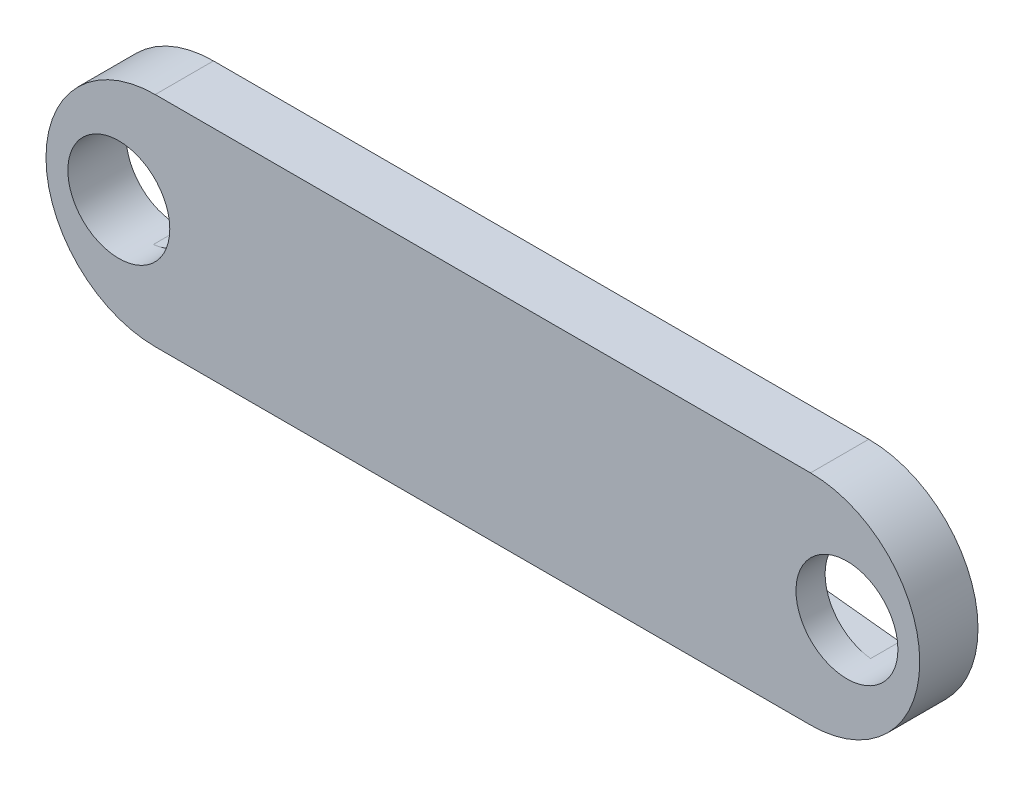
SolidWorks part; units mm, degrees
ref_plane "Front Plane" through (0, 0, 0) normal (0, 0, 1) x (1, 0, 0)
ref_plane "Top Plane" through (0, 0, 0) normal (0, 1, 0) x (1, 0, 0)
ref_plane "Right Plane" through (0, 0, 0) normal (1, 0, 0) x (0, 0, -1)
sketch "Sketch1" plane through (0, 0, 0) normal (0, 0, 1) x (1, 0, 0)
  line L1 (-55, 16.6867) -> (5, 16.6867)
  line L2 (-55, 16.6867) -> (-55, 1.6867)
  line L3 (-55, 1.6867) -> (5, 1.6867)
  line L4 (5, 16.6867) -> (5, 1.6867)
  line L5 (-55, 16.6867) -> (5, 1.6867) construction
  line L6 (-55, 1.6867) -> (5, 16.6867) construction
  circle A0 centre (-50, 9.1867) radius 1
  circle A1 centre (0, 9.1867) radius 1
  point P0 (-25, 9.1867)
  dimension "D1" = 60
  dimension "D2" = 15
extrude "Boss-Extrude1" add sketch "Sketch1" along normal blind 4
fillet "Fillet1" 2 edges at (5, 16.6867, 2) (5, 1.6867, 2) type full round first side face at (-25, 16.6867, 2) second side face at (-25, 1.6867, 2) middle face at (5, 9.1867, 2)
fillet "Fillet2" 2 edges at (-55, 1.6867, 2) (-55, 16.6867, 2) type full round first side face at (-28.75, 1.6867, 2) second side face at (-28.75, 16.6867, 2) middle face at (-55, 9.1867, 2)
sketch "Sketch3" plane through (0, 0, 0) normal (0, 0, -1) x (-1, 0, 0)
  line L0 (14.2143, 11.1752) -> (0.375, 12.6666)
  line L1 (14.2143, 7.1983) -> (0.375, 5.7069)
  arc A0 (0.375, 5.7069) -> (0.375, 12.6666) centre (0, 9.1867) cw
  arc A1 (14.2143, 11.1752) -> (14.2143, 7.1983) centre (14, 9.1867) cw
extrude "Cut-Extrude1" cut sketch "Sketch3" against normal blind 2
sketch "Sketch4" plane through (0, 0, 2) normal (0, 0, -1) x (-1, 0, 0)
  circle A1 centre (0, 9.1867) radius 3.5
extrude "Cut-Extrude2" cut sketch "Sketch4" against normal blind 6
sketch "Sketch5" plane through (0, 0, 0) normal (0, 0, -1) x (-1, 0, 0)
  line L0 (49.625, 12.6666) -> (35.7857, 11.1752)
  line L1 (35.7857, 7.1983) -> (49.625, 5.7069)
  arc A0 (49.625, 12.6666) -> (49.625, 5.7069) centre (50, 9.1867) cw
  arc A1 (35.7857, 11.1752) -> (35.7857, 7.1983) centre (36, 9.1867) ccw
extrude "Cut-Extrude3" cut sketch "Sketch5" against normal blind 2
sketch "Sketch6" plane through (0, 0, 0) normal (0, 0, -1) x (-1, 0, 0)
  circle A1 centre (50, 9.1867) radius 3.5
extrude "Cut-Extrude4" cut sketch "Sketch6" against normal blind 6
